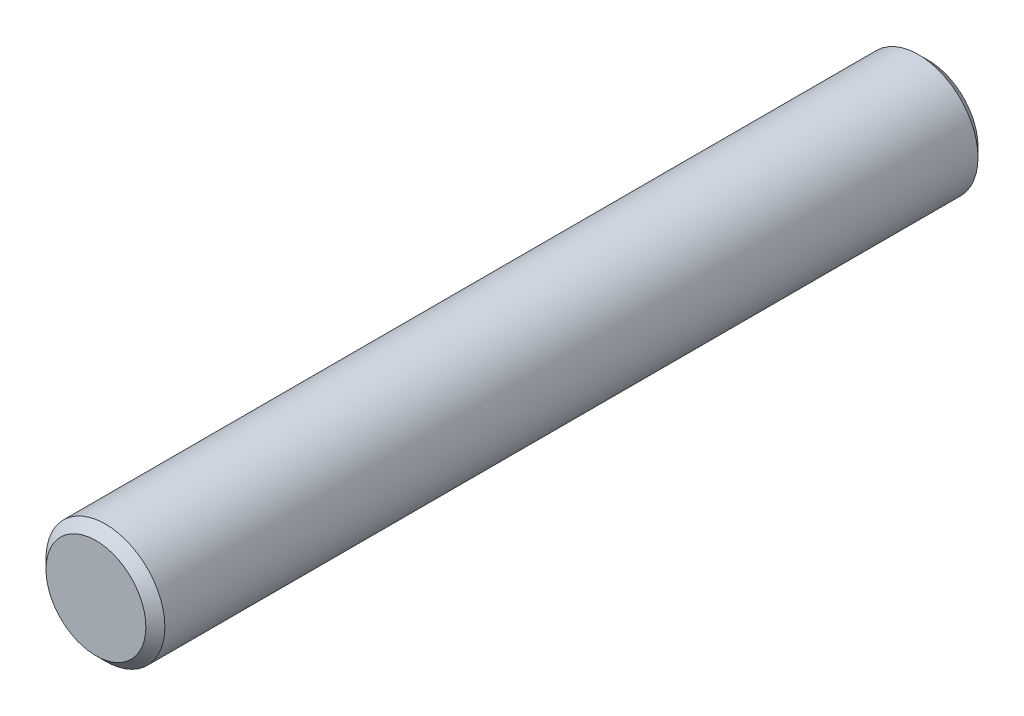
SolidWorks part; units mm, degrees
material "Plain Carbon Steel"
ref_plane "Front Plane" through (0, 0, 0) normal (0, 0, 1) x (1, 0, 0)
ref_plane "Top Plane" through (0, 0, 0) normal (0, 1, 0) x (1, 0, 0)
ref_plane "Right Plane" through (0, 0, 0) normal (1, 0, 0) x (0, 0, -1)
ref_axis "X-axis" through (-88.99, 0, 0) along (1, 0, 0)
ref_axis "Y-axis" through (0, 55, 0) along (0, -1, 0)
ref_axis "Z-axis" through (0, 0, -88.99) along (0, 0, 1)
sketch "Sketch1" plane through (0, 0, 0) normal (0, 0, 1) x (1, 0, 0)
  circle A0 centre (0, 0) radius 1.5875
  dimension "D1" = 3.175
extrude "Boss-Extrude1" add sketch "Sketch1" against normal blind 22.225
chamfer "Chamfer1" distance 0.254 angle 45 2 edges at (1.5875, 0, -22.225) (1.5875, 0, 0)
